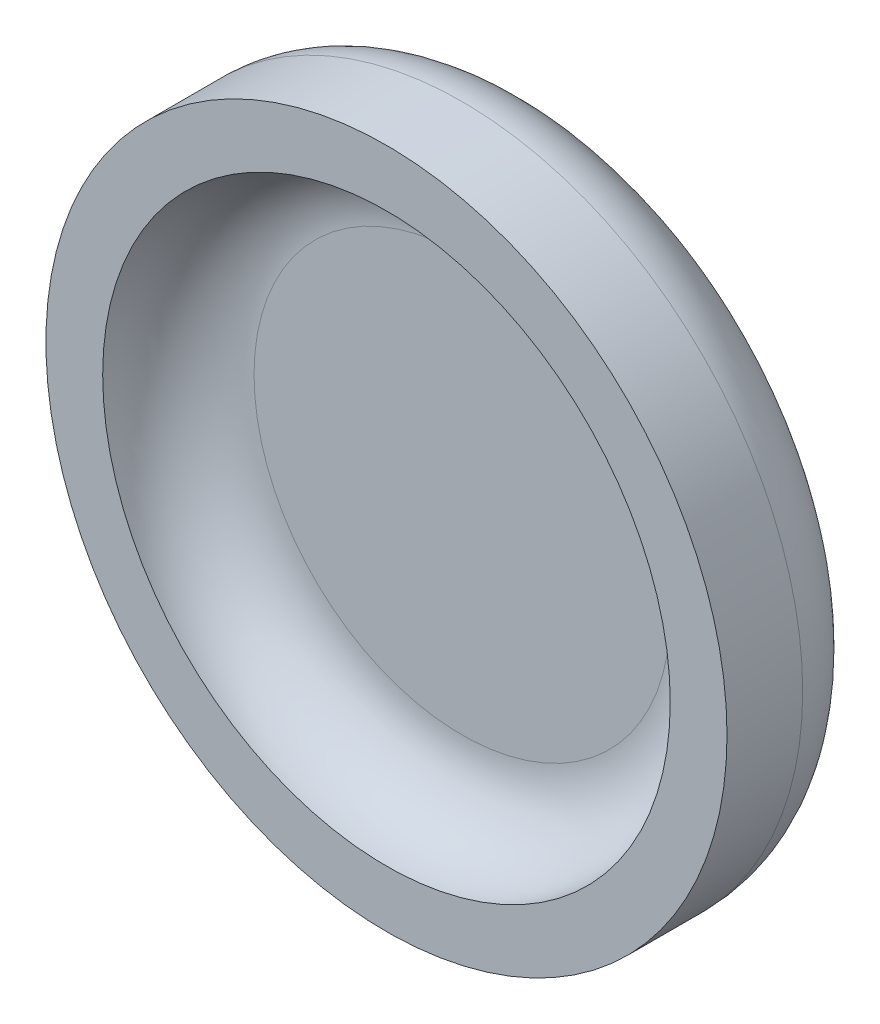
SolidWorks part; units mm, degrees
ref_plane "Front Plane" through (0, 0, 0) normal (0, 0, 1) x (1, 0, 0)
ref_plane "Top Plane" through (0, 0, 0) normal (0, 1, 0) x (1, 0, 0)
ref_plane "Right Plane" through (0, 0, 0) normal (1, 0, 0) x (0, 0, -1)
sketch "Sketch1" plane through (0, 0, 0) normal (0, 0, 1) x (1, 0, 0)
  circle A0 centre (0, 0) radius 9
  dimension "D1" = 18
extrude "Boss-Extrude1" add sketch "Sketch1" along normal blind 4
sketch "Sketch2" plane through (0, 0, 4) normal (0, 0, 1) x (1, 0, 0)
  circle A0 centre (0, 0) radius 7.5
  dimension "D1" = 15
extrude "Cut-Extrude1" cut sketch "Sketch2" against normal blind 2
fillet "Fillet1" radius 2 1 edges at (9, 0, 0)
fillet "Fillet2" radius 2 1 edges at (7.5, 0, 2)
